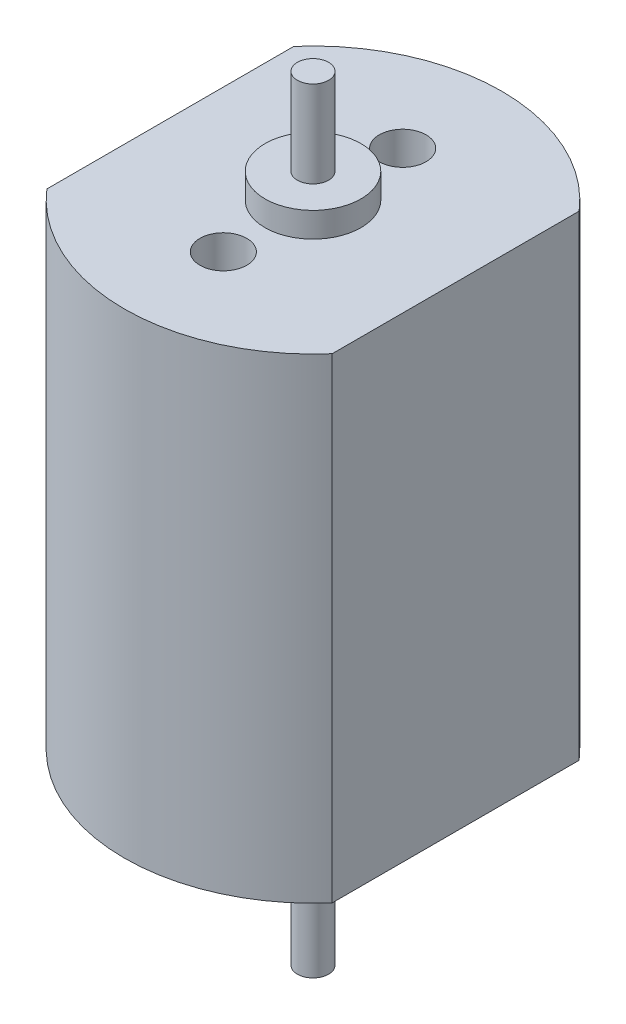
SolidWorks part; units mm, degrees
ref_plane "Front Plane" through (0, 0, 0) normal (0, 0, 1) x (1, 0, 0)
ref_plane "Top Plane" through (0, 0, 0) normal (0, 1, 0) x (1, 0, 0)
ref_plane "Right Plane" through (0, 0, 0) normal (1, 0, 0) x (0, 0, -1)
sketch "Sketch1" plane through (0, 0, 0) normal (0, 1, 0) x (1, 0, 0)
  line L4 (-9.15, 7.9175) -> (-9.15, -7.9175)
  line L5 (9.15, 7.9175) -> (9.15, -7.9175)
  arc A0 (9.15, 7.9175) -> (-9.15, 7.9175) centre (0, 0) ccw
  arc A1 (-9.15, -7.9175) -> (9.15, -7.9175) centre (0, 0) ccw
  circle A2 centre (0, 0) radius 1.03 construction
  point P7 (0, 0)
  dimension "D1" = 24.2
  dimension "D3" = 2.06
  dimension "D2" = 18.3
extrude "Boss-Extrude1" add sketch "Sketch1" along normal blind 30.5
sketch "Sketch2" plane through (0, 30.5, 0) normal (0, 1, 0) x (1, 0, 0)
  circle A0 centre (0, 0) radius 3.075
  circle A1 centre (0, 0) radius 1
  dimension "D1" = 6.15
  dimension "D2" = 2
extrude "Boss-Extrude2" add sketch "Sketch2" along normal blind 1.6
extrude "Boss-Extrude3" add sketch "Sketch2<2>" along normal blind 7.15 contours A1 region at (0, 30.5, 0)
sketch "Sketch2<2>" plane through (0, 30.5, 0) normal (0, 1, 0) x (1, 0, 0) same geometry as "Sketch2"
sketch "Sketch3" plane through (0, 0, 0) normal (0, -1, 0) x (1, 0, 0)
  circle A0 centre (0, 0) radius 4
  circle A1 centre (0, 0) radius 1
  dimension "D1" = 8
  dimension "D2" = 2
extrude "Boss-Extrude4" add sketch "Sketch3" along normal blind 2
extrude "Boss-Extrude5" add sketch "Sketch3<2>" along normal blind 12 contours A1 region at (0, 0, 0)
sketch "Sketch3<2>" plane through (0, 0, 0) normal (0, -1, 0) x (1, 0, 0) same geometry as "Sketch3"
sketch "Sketch4" plane through (0, 30.5, 0) normal (0, 1, 0) x (1, 0, 0)
  line L0 (0, -5.75) -> (0, 5.75) construction
  circle A0 centre (0, 5.75) radius 1.5
  circle A1 centre (0, -5.75) radius 1.5
  point P2 (0, 0)
  dimension "D2" = 3
  dimension "D1" = 11.5
extrude "Cut-Extrude1" cut sketch "Sketch4" against normal blind 5
